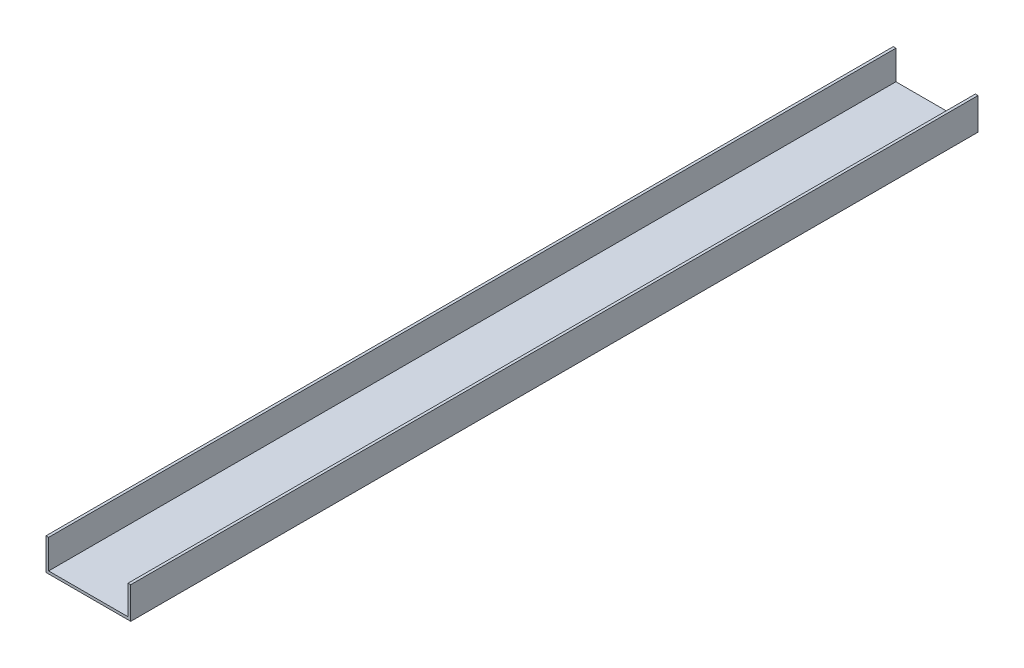
SolidWorks part; units mm, degrees
ref_plane "Front" through (0, 0, 0) normal (0, 0, 1) x (1, 0, 0)
ref_plane "Top" through (0, 0, 0) normal (0, 1, 0) x (1, 0, 0)
ref_plane "Right" through (0, 0, 0) normal (1, 0, 0) x (0, 0, -1)
sketch "Sketch1" plane through (0, 0, 0) normal (0, 0, 1) x (1, 0, 0)
  line L0 (0, -9.525) -> (0, 9.525) construction
  line L1 (-25.4, 0) -> (25.4, 0) construction
  line L2 (23.8125, 9.525) -> (-23.8125, 9.525) construction
  line L3 (-25.4, -9.525) -> (25.4, -9.525)
  line L4 (-25.4, -9.525) -> (-25.4, 9.525)
  line L5 (-25.4, 9.525) -> (25.4, 9.525)
  line L6 (25.4, -9.525) -> (25.4, 9.525)
  line L7 (-25.4, -9.525) -> (25.4, 9.525) construction
  line L8 (-25.4, 9.525) -> (25.4, -9.525) construction
  line L9 (-23.8125, -9.525) -> (23.8125, -9.525)
  point P3 (0, 0)
  point P4 (0, 0)
  point P8 (0, 0)
  point P13 (25.4, -7.9375)
  point P17 (0, 9.525)
  point P20 (0, -9.525)
  dimension "Outside Width" = 50.8
  dimension "Outside Height" = 19.05
  dimension "Inside Height" = 17.4625
  dimension "Wall Thickness" = 1.5875
  dimension "Inside Width" = 47.625
sketch "Sketch2" plane through (0, 0, 0) normal (1, 0, 0) x (0, 0, -1)
  line L0 (-254, 0) -> (254, 0) construction
  dimension "Length" = 508
sketch "Sketch3" plane through (0, 0, 0) normal (0, 0, 1) x (1, 0, 0)
  line L0 (-25.4, 9.525) -> (-25.4, -9.525)
  line L1 (-25.4, -9.525) -> (25.4, -9.525)
  line L2 (25.4, -9.525) -> (25.4, 9.525)
  line L3 (25.4, 9.525) -> (23.8125, 9.525)
  line L4 (23.8125, 9.525) -> (23.8125, -7.9375)
  line L5 (23.8125, -7.9375) -> (-23.8125, -7.9375)
  line L6 (-23.8125, -7.9375) -> (-23.8125, 9.525)
  line L7 (-23.8125, 9.525) -> (-25.4, 9.525)
  line L8 (-23.8125, -7.9375) -> (-23.8125, -9.525) construction
  dimension "D1" = 19.05
  dimension "D2" = 50.8
  dimension "D3" = 1.5875
extrude "Boss-Extrude2" add sketch "Sketch3" along normal mid plane 508
sketch "Reference Sketch1" plane through (0, 0, 0) normal (1, 0, 0) x (0, 0, -1)
  line L0 (-254, 0) -> (254, 0) construction
  point P0 (-220.6625, 0)
  point P1 (220.6625, 0)
  dimension "D1" = 33.3375
  dimension "D2" = 33.3375
equation "\"D1@Sketch3\" = \"Outside Height@Sketch1\""
equation "\"D2@Sketch3\" = \"Outside Width@Sketch1\""
equation "\"D3@Sketch3\" = \"Wall Thickness@Sketch1\""
equation "\"D1@Reference Sketch1\"=\"Outside Height@Sketch1\" * 1.75"
equation "\"D2@Reference Sketch1\" = \"D1@Reference Sketch1\""
equation "\"D1@Boss-Extrude2\" = \"Length@Sketch2\""
equation "\"Inside Height@Sketch1\"=\"Outside Height@Sketch1\"-\"Wall Thickness@Sketch1\""
equation "\"Inside Width@Sketch1\"=\"Outside Width@Sketch1\"-\"Wall Thickness@Sketch1\"*2"
